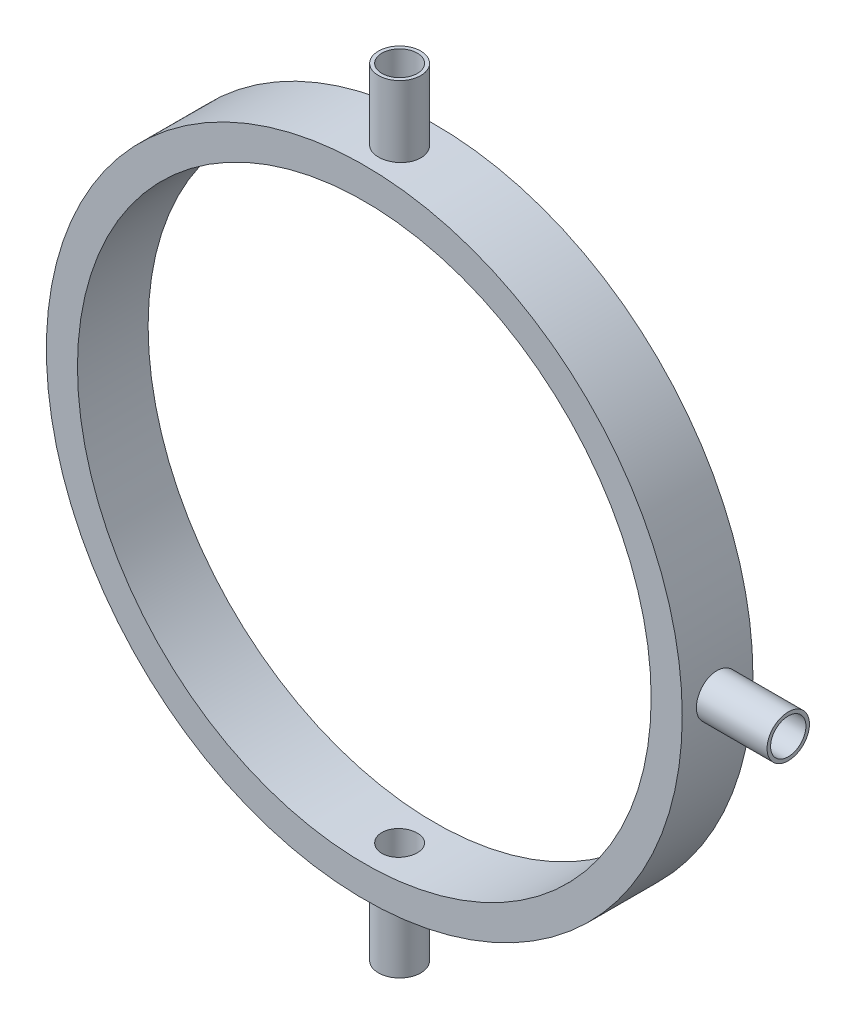
SolidWorks part; units mm, degrees
material "Nylon 101"
ref_plane "Front Plane" through (0, 0, 0) normal (0, 0, 1) x (1, 0, 0)
ref_plane "Top Plane" through (0, 0, 0) normal (0, 1, 0) x (1, 0, 0)
ref_plane "Right Plane" through (0, 0, 0) normal (1, 0, 0) x (0, 0, -1)
sketch "Sketch1" plane through (0, 0, 0) normal (0, 0, 1) x (1, 0, 0)
  circle A0 centre (0, 0) radius 57.15
  dimension "D1" = 114.3
extrude "Boss-Extrude1" add sketch "Sketch1" along normal mid plane 12.7
sketch "Sketch2" plane through (0, 0, 0) normal (1, 0, 0) x (0, 0, -1)
  circle A0 centre (0, 0) radius 3.175
  circle A1 centre (0, 0) radius 3.81
  dimension "D2" = 6.35
  dimension "D3" = 7.62
extrude "Boss-Extrude2" add sketch "Sketch2" along normal blind 69.85
sketch "Sketch3" plane through (0, 0, 0) normal (0, 1, 0) x (1, 0, 0)
  circle A0 centre (0, 0) radius 3.81
  circle A1 centre (0, 0) radius 3.175
  dimension "D2" = 7.62
  dimension "D3" = 6.35
extrude "Boss-Extrude3" add sketch "Sketch3" along normal mid plane 139.7
sketch "Sketch4" plane through (0, 0, 6.35) normal (0, 0, 1) x (1, 0, 0)
  circle A0 centre (0, 0) radius 51.562
  dimension "D1" = 103.124
extrude "Cut-Extrude1" cut sketch "Sketch4" against normal through all
sketch "Sketch5" plane through (0, -69.85, 0) normal (0, -1, 0) x (1, 0, 0)
  circle A0 centre (0, 0) radius 3.175
  dimension "D1" = 6.35
extrude "Cut-Extrude2" cut sketch "Sketch5" against normal through all
sketch "Sketch6" plane through (69.85, 0, 0) normal (1, 0, 0) x (0, 0, -1)
  circle A0 centre (0, 0) radius 3.175
  dimension "D1" = 6.35
extrude "Cut-Extrude3" cut sketch "Sketch6" against normal up to next
